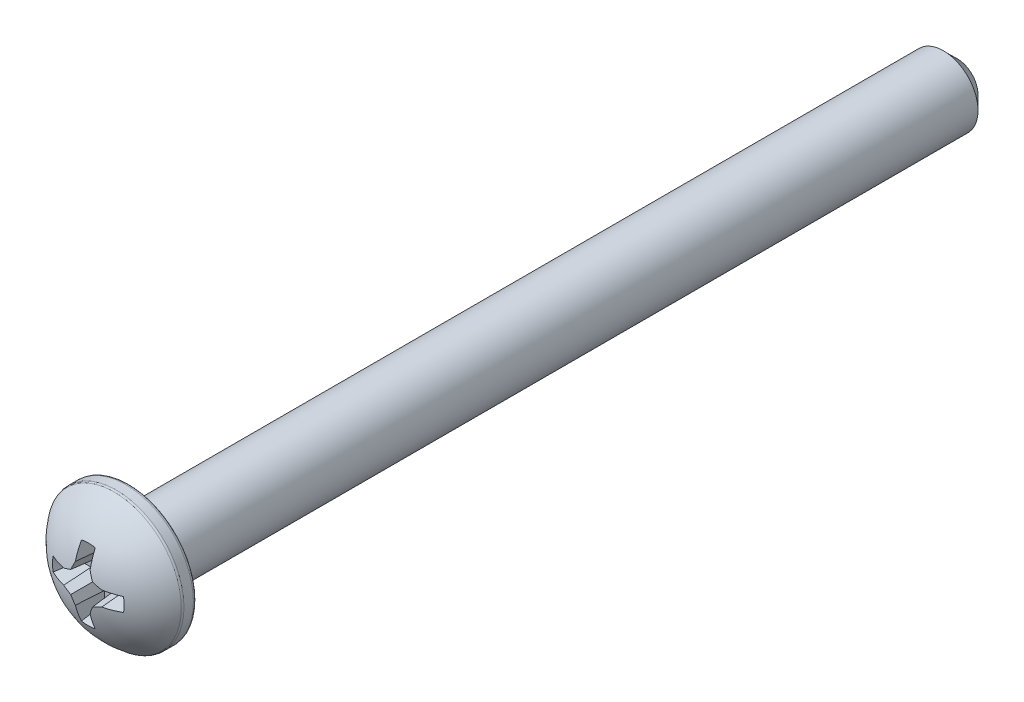
SolidWorks part; units mm, degrees
note: '?' marks a value the reader was unsure of.
ref_plane "Front Plane" through (0, 0, 0) normal (0, 0, 1) x (1, 0, 0)
ref_plane "Top Plane" through (0, 0, 0) normal (0, 1, 0) x (1, 0, 0)
ref_plane "Right Plane" through (0, 0, 0) normal (1, 0, 0) x (0, 0, -1)
sketch "Sketch1" plane through (0, 0, 0) normal (1, 0, 0) x (0, 0, -1)
  line L0 (-20.1803, 0) -> (20.1803, 0) construction
  line L1 (20.1803, 1.5875) -> (20.1803, -1.5875) construction
  line L2 (-17.9197, 3.1115) -> (-17.9197, -3.1115) construction
  line L3 (20.1406, 1.6562) -> (20.7756, 1.6562) construction
  line L4 (20.1406, 1.6562) -> (20.4581, 1.1063) construction
  line L5 (20.4581, 1.1063) -> (20.7756, 1.6562) construction
  line L6 (20.4581, 1.6562) -> (20.4581, 1.5875) construction
  line L7 (20.4581, 1.1063) -> (20.4581, 1.1751) construction
  line L8 (20.1803, 1.5875) -> (20.7359, 1.5875) construction
  line L9 (20.1605, 1.6219) -> (20.7558, 1.6219) construction
  line L10 (20.4184, 1.1751) -> (20.4978, 1.1751) construction
  line L11 (-20.1803, 1.75) -> (-20.1803, -1.75) construction
  point P4 (0, 0)
  point P8 (20.1803, 0)
  point P11 (-17.9197, 0)
  point P16 (17.9578, -1.5875)
  point P20 (20.4581, 1.5875)
  point P23 (20.4581, 1.6219)
  point P26 (20.4581, 1.1751)
  point P31 (-20.1803, 0)
  dimension "D2" = 0.0794
  dimension "D1" = 2.2225
sketch "Sketch2" plane through (0, 0, 0) normal (1, 0, 0) x (0, 0, -1)
  line L0 (20.1803, 0) -> (20.1803, 0.9525)
  line L1 (20.1803, 1.5875) -> (20.1803, -1.5875) construction
  line L2 (20.1803, 0.9525) -> (19.5453, 1.5875)
  line L3 (19.5453, 1.5875) -> (-17.9197, 1.5875)
  line L4 (-17.9197, 3.1115) -> (-17.9197, -3.1115) construction
  line L5 (-17.9197, 1.5875) -> (-17.9197, 2.95)
  line L6 (-18.0812, 3.1115) -> (-18.5138, 3.1115)
  line L7 (-20.1803, 0) -> (20.1803, 0) construction
  line L8 (-20.1803, 0) -> (20.1803, 0) construction
  line L9 (20.1803, 0) -> (-20.1803, 0)
  arc A0 (-18.6086, 3.0808) -> (-20.1803, 0) centre (-16.3751, 0) ccw
  arc A1 (-18.5138, 3.1115) -> (-18.6086, 3.0808) centre (-18.5138, 2.95) ccw
  arc A2 (-17.9197, 2.95) -> (-18.0812, 3.1115) centre (-18.0812, 2.95) ccw
  point P20 (-18.5656, 3.1115)
  point P26 (-17.9197, 3.1115)
  dimension "D4" = 0.1615
  dimension "D1" = 0.635
  dimension "D2" = 45
  dimension "D3" = 0.6459
revolve "Revolve1" add sketch "Sketch2" angle 360 about L8
ref_plane "Plane1" through (0, 0, 20.1803) normal (0, 0, 1) x (1, 0, 0)
sketch "Sketch3" plane through (0, 0, 20.1803) normal (0, 0, 1) x (1, 0, 0)
  line L0 (0.35, 0.875) -> (0.5038, 0.5038)
  line L1 (0.35, 1.7146) -> (0.35, 0.875)
  line L2 (0.875, 0.35) -> (1.7146, 0.35)
  line L3 (0.875, 0.35) -> (0.5038, 0.5038)
  line L4 (0.875, -0.35) -> (0.875, 0.35) construction
  line L5 (0.35, 0.875) -> (0.875, 0.35) construction
  line L6 (0.6125, 0.6125) -> (0, 0) construction
  line L7 (0, 0) -> (1.75, 0) construction
  line L8 (0, 0) -> (0, 1.75) construction
  line L9 (-0.875, 0.35) -> (-1.7146, 0.35)
  line L10 (-0.875, 0.35) -> (-0.5038, 0.5038)
  line L11 (-0.35, 0.875) -> (-0.5038, 0.5038)
  line L12 (-0.35, 1.7146) -> (-0.35, 0.875)
  line L13 (0.875, -0.35) -> (1.7146, -0.35)
  line L14 (0.35, -1.7146) -> (0.35, -0.875)
  line L15 (0.35, -0.875) -> (0.5038, -0.5038)
  line L16 (0.875, -0.35) -> (0.5038, -0.5038)
  line L17 (-0.875, -0.35) -> (-1.7146, -0.35)
  line L18 (-0.35, -1.7146) -> (-0.35, -0.875)
  line L19 (-0.35, -0.875) -> (-0.5038, -0.5038)
  line L20 (-0.875, -0.35) -> (-0.5038, -0.5038)
  circle A0 centre (0, 0) radius 1.75 construction
  arc A1 (-1.7146, 0.35) -> (-1.7146, -0.35) centre (0, 0) ccw
  arc A2 (-0.35, -1.7146) -> (0.35, -1.7146) centre (0, 0) ccw
  arc A3 (1.7146, 0.35) -> (1.7146, -0.35) centre (0, 0) cw
  arc A4 (-0.35, 1.7146) -> (0.35, 1.7146) centre (0, 0) cw
  point P11 (0.875, 0)
  dimension "D2" = 0.7
  dimension "D3" = 0.7
  dimension "D1" = 22.5
extrude "Cut-Extrude1" cut sketch "Sketch3" against normal blind 1.3564
draft "Draft1" type of draft neutral plane draft angle 15 neutral plane "Plane1" faces to draft 4 face at (1.7323, 0, 19.289) face at (0, 1.7323, 19.289) face at (0, -1.7323, 19.289) face at (-1.7323, 0, 19.289) neutral plane through (0, 0, 20.1803) neutral plane normal (0, 0, 1) parameters "D1"=15
draft "Draft2" type of draft neutral plane draft angle 5 neutral plane "Plane1" faces to draft 16 face at (0.35, 1.1437, 19.2607) face at (1.1437, -0.35, 19.2607) face at (0.35, -1.1437, 19.2607) face at (-0.35, -1.1437, 19.2607) face at (-1.1437, -0.35, 19.2607) face at (-1.1437, 0.35, 19.2607) face at (-0.35, 1.1437, 19.2607) face at (1.1437, 0.35, 19.2607) face at (0.6895, 0.4268, 19.457) face at (0.4268, 0.6895, 19.457) face at (0.6895, -0.4268, 19.457) face at (0.4268, -0.6895, 19.457) face at (-0.4268, -0.6895, 19.457) face at (-0.6895, -0.4268, 19.457) face at (-0.6895, 0.4268, 19.457) face at (-0.4268, 0.6895, 19.457) neutral plane through (0, 0, 20.1803) neutral plane normal (0, 0, 1) parameters "D1"=5
ref_axis "Center Axis1" through (0, 0, -87.463) along (0, 0, 1)?
ref_plane "Contact Plane1" through (0, 0, -20.1803) normal (0, 0, 1) x (1, 0, 0)
ref_plane "Contact Plane2" through (0, 0, 17.9197) normal (0, 0, 1) x (1, 0, 0)
equation "\"D2@Sketch1\" = \"Pitch@Sketch1\" / 8"
equation "\"D1@Sketch1\"=\"Pitch@Sketch1\"*3.50"
equation "\"D1@Sketch2\"=\"Pitch@Sketch1\""
equation "\"D3@Sketch2\"=\"Head Height@Sketch1\"/3.5"
equation "\"D4@Sketch2\"=\"D3@Sketch2\"/4"
equation "\"D3@Sketch3\"=\"D2@Sketch3\""
equation "\"D1@Cut-Extrude1\" = \"Head Height@Sketch1\" * .6"
equation "\"D2@Sketch3\"=\"Drive Size@Sketch1\"/5"
equation "\"D4@Helix/Spiral1\"=\"Pitch@sketch1\""
equation "\"D3@Helix/Spiral1\"=\"Length@sketch1\"+\"D4@Helix/Spiral1\""
